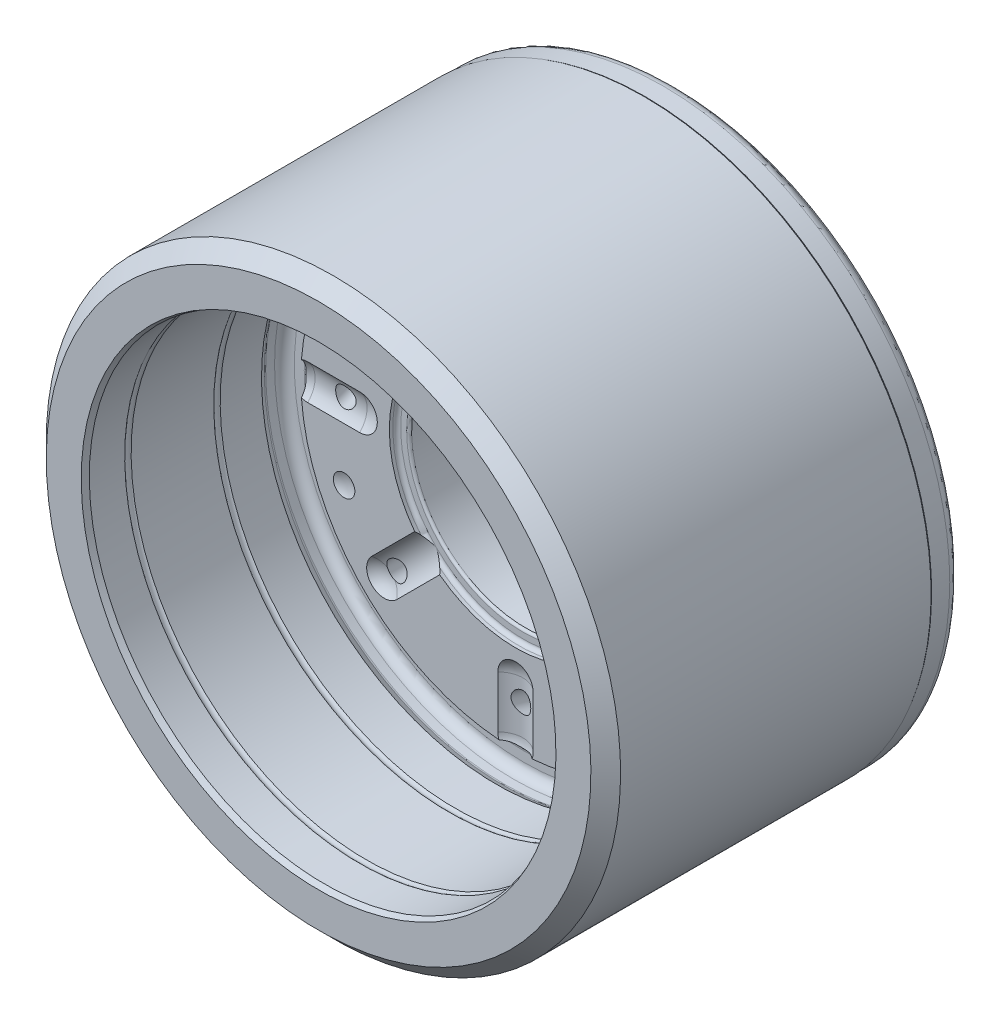
SolidWorks part; units mm, degrees
material "PB01 (C90710) Bronze"
ref_plane "Front Plane" through (0, 0, 0) normal (0, 0, 1) x (1, 0, 0)
ref_plane "Top Plane" through (0, 0, 0) normal (0, 1, 0) x (1, 0, 0)
ref_plane "Right Plane" through (0, 0, 0) normal (1, 0, 0) x (0, 0, -1)
sketch "Sketch1" plane through (0, 0, 0) normal (1, 0, 0) x (0, 0, -1)
  line L0 (18.8225, 47.5494) -> (18.8225, -47.4506) construction
  line L1 (0, 47.9768) -> (1.2, 47.54)
  line L2 (19.397, 0) -> (-16.248, 0) construction
  line L3 (1.2, 47.54) -> (8.35, 47.54)
  line L4 (0, 47.9768) -> (0, 55.04)
  line L5 (0, 55.04) -> (3, 58.04)
  line L6 (3, 58.04) -> (65.7575, 58.04)
  line L7 (66, 57.9) -> (70.5, 57.9)
  line L8 (70.5, 57.9) -> (72, 56.4)
  line L9 (72, 56.4) -> (72, 47.3501)
  line L10 (66, 57.9) -> (65.7575, 58.04)
  line L11 (36, 47.54) -> (37.3039, 48.2928)
  line L12 (37.7039, 48.4) -> (39.5, 48.4)
  line L13 (41.5, 46.4) -> (41.5, 44.4)
  line L14 (40.5, 43.4) -> (39.8, 43.4)
  line L15 (39.8, 25.5) -> (39.8, 43.4)
  line L16 (39.8, 25.5) -> (40.5, 25.5)
  line L17 (41.3, 24.7) -> (41.3, 23.5)
  line L18 (41.8, 23) -> (68, 23)
  line L19 (68.5, 23.5) -> (68.5, 25.7)
  line L20 (69.3, 26.5) -> (71.5, 26.5)
  line L21 (72, 27) -> (72, 37.5)
  line L22 (71.5, 38) -> (69, 38)
  line L23 (71.671, 46.8803) -> (68.316, 45.6591)
  line L24 (67, 43.7797) -> (67, 40)
  line L25 (9.65, 47.54) -> (26.35, 47.54)
  line L26 (27.65, 47.54) -> (36, 47.54)
  arc A0 (67, 40) -> (69, 38) centre (69, 40) ccw
  arc A1 (68.316, 45.6591) -> (67, 43.7797) centre (69, 43.7797) ccw
  arc A2 (39.5, 48.4) -> (41.5, 46.4) centre (39.5, 46.4) cw
  arc A3 (41.5, 44.4) -> (40.5, 43.4) centre (40.5, 44.4) cw
  arc A4 (8.35, 47.54) -> (9.65, 47.54) centre (9, 46.7801) cw
  arc A5 (26.35, 47.54) -> (27.65, 47.54) centre (27, 46.7801) cw
  arc A6 (40.5, 25.5) -> (41.3, 24.7) centre (40.5, 24.7) cw
  arc A7 (71.5, 26.5) -> (72, 27) centre (71.5, 27) ccw
  arc A8 (68, 23) -> (68.5, 23.5) centre (68, 23.5) ccw
  arc A9 (41.3, 23.5) -> (41.8, 23) centre (41.8, 23.5) ccw
  arc A10 (68.5, 25.7) -> (69.3, 26.5) centre (69.3, 25.7) cw
  arc A11 (37.3039, 48.2928) -> (37.7039, 48.4) centre (37.7039, 47.6) cw
  arc A12 (72, 37.5) -> (71.5, 38) centre (71.5, 37.5) ccw
  arc A13 (72, 47.3501) -> (71.671, 46.8803) centre (71.5, 47.3501) cw
  point P58 (72, 47)
  dimension "D28" = 2
  dimension "D29" = 2
  dimension "D31" = 2
  dimension "D32" = 1
  dimension "D33" = 1.3
  dimension "D34" = 1
  dimension "D35" = 9
  dimension "D37" = 18
  dimension "D38" = 0.8
  dimension "D39" = 0.5
  dimension "D40" = 0.8
  dimension "D41" = 0.8
  dimension "D42" = 0.5
  dimension "D1" = 95
  dimension "D2" = 95.08
  dimension "D3" = 116.08
  dimension "D4" = 72
  dimension "D5" = 115.8
  dimension "D6" = 5
  dimension "D7" = 6
  dimension "D8" = 1.5
  dimension "D9" = 45
  dimension "D10" = 30
  dimension "D11" = 3
  dimension "D12" = 45
  dimension "D13" = 1.2
  dimension "D14" = 20
  dimension "D15" = 36
  dimension "D16" = 41.5
  dimension "D17" = 96.8
  dimension "D18" = 32.2
  dimension "D19" = 86.8
  dimension "D20" = 1.5
  dimension "D21" = 51
  dimension "D22" = 53
  dimension "D23" = 46
  dimension "D24" = 3.5
  dimension "D25" = 76
  dimension "D26" = 94
  dimension "D27" = 70
  dimension "D30" = 30
  dimension "D36" = 2
revolve "Revolve1" add sketch "Sketch1" angle 360 about L2
fillet "Fillet1" radius 2 1 edges at (0, 57.9, -70.5)
sketch "Sketch2" plane through (0, 0, 0) normal (1, 0, 0) x (0, 0, -1)
  line L0 (36.3, 49.5383) -> (36.3, 6.7898) construction
  line L1 (41.3, 42) -> (41.3, 31.5)
  line L4 (39.8, 25.5) -> (39.8, 43.4) construction
  line L5 (19.397, 0) -> (-16.248, 0) construction
  line L6 (36.3, 47) -> (-1.3522, 47) construction
  line L7 (36.3, 26.5) -> (36.3, 47)
  arc A0 (41.3, 42) -> (36.3, 47) centre (36.3, 42) ccw
  arc A1 (41.3, 31.5) -> (36.3, 26.5) centre (36.3, 31.5) cw
  dimension "D1" = 5
  dimension "D3" = 42
  dimension "D5" = 5
  dimension "D6" = 31.5
  dimension "D2" = 1.5
revolve "Cut-Revolve1" cut sketch "Sketch2" angle 360 about L7
pattern_circular "CirPattern1" count 4 over 360 about axis through (0, 0, -19.397) along (0, 0, -1) of "Cut-Revolve1"
ref_axis "Axis1" through (0, 0, -75.9566) along (0, 0, 1)
ref_plane "Plane1" through (0, 0, 0) normal (0.7071, 0.7071, 0) x (0, 0, 1)
sketch "Sketch3" plane through (0, 0, 0) normal (0.7071, 0.7071, 0) x (0, 0, 1)
  line L0 (-41.3, 37.5) -> (-41.3, 8.7918)
  line L1 (-36.3, 0.7828) -> (-36.3, 47.4991) construction
  line L2 (-39.8, -25.5) -> (-39.8, 25.5) construction
  line L3 (-41.3, 8.7918) -> (-36.3, 8.7918)
  line L4 (-36.3, 8.7918) -> (-36.3, 42.5)
  line L5 (-19.397, 0) -> (16.248, 0) construction
  arc A0 (-36.3, 42.5) -> (-41.3, 37.5) centre (-36.3, 37.5) ccw
  dimension "D1" = 1.5
  dimension "D2" = 5
  dimension "D3" = 37.5
  dimension "D4" = 8.7918
revolve "Cut-Revolve2" cut sketch "Sketch3" angle 360 about L1
pattern_circular "CirPattern3" count 4 over 360 about axis through (0, 0, -19.397) along (0, 0, -1) of "Cut-Revolve2"
sketch "Sketch4" plane through (0, 0, 0) normal (1, 0, 0) x (0, 0, -1)
  line L0 (72, 44) -> (15.3231, 28.8135) construction
  line L1 (72, -56.4) -> (72, 56.4) construction
  line L2 (19.397, 0) -> (-16.248, 0) construction
  line L3 (71.4824, 45.9319) -> (34.7772, 36.0967)
  line L4 (72, 44) -> (71.4824, 45.9319)
  line L5 (34.7772, 36.0967) -> (34.134, 33.8538)
  line L6 (72, 44) -> (34.134, 33.8538)
  dimension "D3" = 4
  dimension "D1" = 15
  dimension "D2" = 44
  dimension "D4" = 59
  dimension "D5" = 38
revolve "4MM HOLE Cut-Revolve3" cut sketch "Sketch4" angle 360 about L6
pattern_circular "CirPattern2" count 8 over 360 about axis through (0, 0, -19.397) along (0, 0, -1) of "4MM HOLE Cut-Revolve3" reverse direction yes
sketch "Sketch9" plane through (0, 0, -39.8) normal (0, 0, 1) x (1, 0, 0)
  line L0 (0, 0) -> (0, 53.843) construction
  line L1 (0, 0) -> (-14.3506, 34.6455) construction
  circle A0 centre (0, 0) radius 37.5
  dimension "D1" = 75
  dimension "D3" = 22.5
ref_plane "Plane2" through (0, 0, 0) normal (-0.9239, -0.3827, 0) x (0, 0, 1)
ref_plane "Plane3" through (0, 0, -39.8) normal (-0.3827, 0.9239, 0) x (0.9239, 0.3827, 0)
sketch "Sketch10" plane through (0, 0, 0) normal (-0.9239, -0.3827, 0) x (0, 0, 1)
  line L0 (-39.8, 37.5) -> (-50.3833, 37.5) construction
  line L1 (-39.8, 0) -> (-39.8, 37.5) construction
  line L2 (-39.8, 11.0517) -> (-39.8, 17.9213) construction
  line L3 (-40.3, 37.5) -> (-18.4723, 37.5)
  line L4 (-18.4723, 42.5) -> (-18.4723, 37.5)
  line L6 (-39.8, 0) -> (-39.8, 49.7445) construction
  line L7 (-39.8, -13.4767) -> (-39.8, 38.7008) construction
  line L8 (-39.8, 39.6794) -> (-39.8, 37.5) construction
  line L9 (-35.3, 42.5) -> (-18.4723, 42.5)
  line L10 (-39.5, 48.4) -> (-39.5, -48.4) construction
  arc A0 (-35.3, 42.5) -> (-40.3, 37.5) centre (-35.3, 37.5) ccw
  dimension "D1" = 0.5
  dimension "D2" = 21.0277
  dimension "D5" = 4.3589
  dimension "D6" = 10
revolve "WEAR INDICATOR Cut-Revolve3" cut sketch "Sketch10" angle 360 about L0
pattern_circular "CirPattern4" count 4 over 360 about axis through (0, 0, -19.397) along (0, 0, -1) of "WEAR INDICATOR Cut-Revolve3" reverse direction yes
sketch "Sketch8" plane through (0, 0, -72) normal (0, 0, -1) x (-1, 0, 0)
  arc A0 (27.6945, 4.1247) -> (-27.9958, 0.4827) centre (0, 0) ccw construction
  text T0 "BG 007 911 71 - A    11111-XX" font "Century Gothic" height 3
  line B0 (2.9172, -34.7359) -> (-1.0049, -34.7359)
  line B1 (2.3363, -33.9363) -> (-0.5503, -33.9363)
  line B2 (-0.9367, -34.6159) -> (-0.6185, -34.0563)
  line B3 (0.5047, -30.6028) -> (-0.1794, -30.6028)
  line B4 (-1.0049, -27.8861) -> (0.5047, -30.6028)
  line B5 (2.3363, -33.9363) -> (0.9149, -31.3596)
  line B6 (4.0702, -31.3596) -> (4.4288, -31.9793)
  line B7 (0.9199, -27.8861) -> (-1.0049, -27.8861)
  line B8 (3.6575, -30.6028) -> (4.0702, -31.3596)
  line B9 (3.6575, -30.6028) -> (2.6209, -28.8549)
  line B10 (-1.0049, -34.7359) -> (-4.0018, -34.7359)
  line B11 (-2.3169, -31.7729) -> (-4.0018, -34.7359)
  line B12 (3.8954, -31.2392) -> (3.5891, -30.7228)
  line B13 (0.9199, -28.0061) -> (-0.8009, -28.0061)
  line B14 (-0.8009, -28.0061) -> (0.642, -30.6028)
  line B15 (-0.1794, -30.7228) -> (3.5891, -30.7228)
  line B16 (-2.2142, -31.8349) -> (-3.7955, -34.6159)
  line B17 (-1.0747, -34.6159) -> (-3.7955, -34.6159)
  line B18 (0.8454, -31.2392) -> (3.8954, -31.2392)
  line B19 (-1.0747, -34.6159) -> (0.8454, -31.2392)
  line B20 (3.9316, -31.3596) -> (4.3262, -32.0417)
  line B21 (2.9172, -34.6159) -> (-0.9367, -34.6159)
  line B22 (0.642, -30.6028) -> (3.518, -30.6028)
  line B23 (3.518, -30.6028) -> (2.5177, -28.9161)
  line B24 (2.5395, -34.0563) -> (-0.6185, -34.0563)
  line B25 (2.5395, -34.0563) -> (1.052, -31.3596)
  line B26 (1.052, -31.3596) -> (3.9316, -31.3596)
  line B27 (-0.5503, -33.9363) -> (0.9149, -31.3596)
  arc B28 (2.6209, -28.8549) -> (0.9199, -27.8861) centre (0.9199, -29.8637) ccw
  arc B29 (2.9172, -34.7359) -> (4.4288, -31.9793) centre (2.9172, -32.9432) ccw
  arc B30 (-0.1794, -30.6028) -> (-2.3169, -31.7729) centre (-0.1794, -33.1404) ccw
  arc B31 (2.5177, -28.9161) -> (0.9199, -28.0061) centre (0.9199, -29.8637) ccw
  arc B32 (-0.1794, -30.7228) -> (-2.2142, -31.8349) centre (-0.1794, -33.1404) ccw
  arc B33 (2.9172, -34.6159) -> (4.3262, -32.0417) centre (2.9172, -32.9432) ccw
  dimension "D1" = 28
sketch_block_instance "SKETCH LOGO-1"
sketch_block "SKETCH LOGO" parameters "D1"=29.059, "D2"=11.4163, "D3"=29.624, "D4"=6.8884
extrude "Cut-Extrude1" cut sketch "Sketch8" against normal blind 0.1
